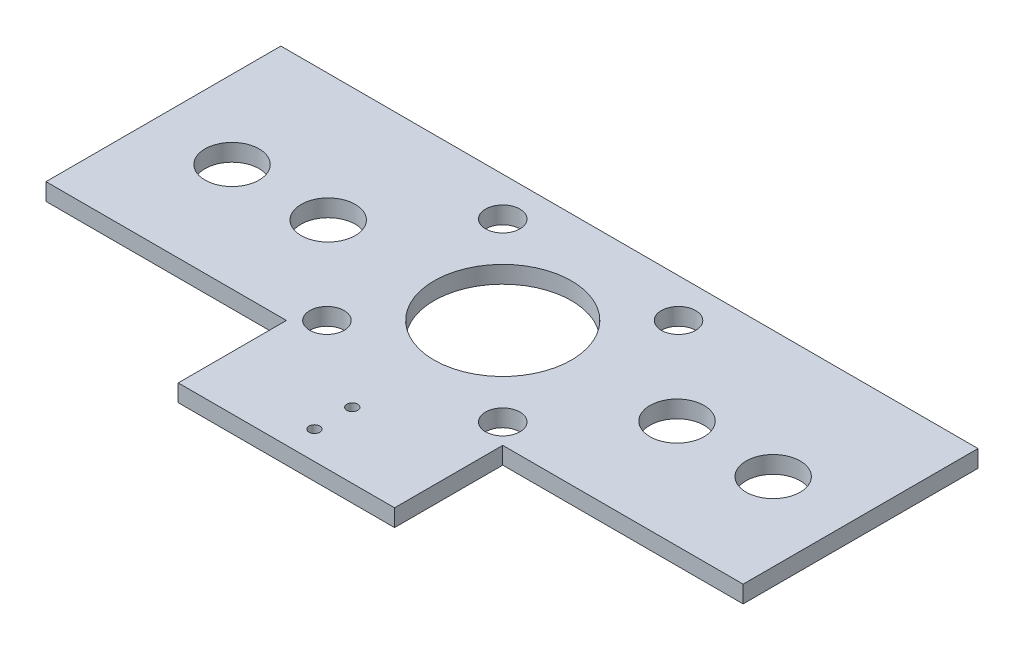
SolidWorks part; units mm, degrees
ref_plane "Front Plane" through (0, 0, 0) normal (0, 0, 1) x (1, 0, 0)
ref_plane "Top Plane" through (0, 0, 0) normal (0, 1, 0) x (1, 0, 0)
ref_plane "Right Plane" through (0, 0, 0) normal (1, 0, 0) x (0, 0, -1)
sketch "plateOutline" plane through (0, 0, 0) normal (0, 1, 0) x (1, 0, 0)
  line L0 (-40, 40) -> (-40, -40)
  line L1 (-40, -40) -> (40, -40)
  line L2 (-40, -40) -> (-40, 40)
  line L4 (40, -40) -> (40, 40)
  line L5 (-40, -40) -> (40, 40) construction
  line L6 (-40, 40) -> (40, -40) construction
  line L7 (-40, -40) -> (40, -40) construction
  line L8 (-40, -40) -> (-40, 40) construction
  line L9 (-40, 40) -> (40, 40) construction
  line L10 (40, -40) -> (40, 40) construction
  line L12 (-40, -40) -> (-128.9, -40)
  line L13 (-128.9, 40) -> (-128.9, -40)
  line L14 (40, 40) -> (40, -40)
  line L16 (40, -40) -> (128.9, -40)
  line L17 (128.9, 40) -> (128.9, -40)
  line L19 (-40, -40) -> (40, -40)
  line L20 (-40, -40) -> (-40, -80)
  line L21 (-40, -80) -> (40, -80)
  line L22 (40, -40) -> (40, -80)
  line L24 (-128.9, 40) -> (-128.9, 46.8499)
  line L25 (-128.9, 46.8499) -> (128.9, 46.8499)
  line L26 (128.9, 40) -> (128.9, 46.8499)
  point P0 (0, 0)
  dimension "D1" = 80
  dimension "D2" = 88.9
  dimension "D3" = 88.9
  dimension "D4" = 40
sketch "railGuides" plane through (0, 0, 0) normal (0, 1, 0) x (1, 0, 0)
  line L1 (-32.5, -32.5) -> (32.5, -32.5) construction
  line L2 (-32.5, -32.5) -> (-32.5, 32.5) construction
  line L3 (-32.5, 32.5) -> (32.5, 32.5) construction
  line L4 (32.5, -32.5) -> (32.5, 32.5) construction
  line L6 (-40, 40) -> (-25, 25) construction
  line L7 (40, 40) -> (25, 25) construction
  line L8 (25, -25) -> (40, -40) construction
  line L9 (-40, -40) -> (-25, -25) construction
  line L10 (-40, 40) -> (-25, 25) construction
  circle A0 centre (-32.5, 32.5) radius 6.35
  circle A1 centre (32.5, 32.5) radius 6.35
  circle A2 centre (32.5, -32.5) radius 6.35
  circle A3 centre (-32.5, -32.5) radius 6.35
sketch "FuelGrainMounting" plane through (0, 0, 0) normal (0, 1, 0) x (1, 0, 0)
  circle A0 centre (0, 0) radius 25.4
extrude "Boss-Extrude1" add sketch "plateOutline" along normal blind 6.35
extrude "Cut-Extrude1" cut sketch "railGuides" along normal blind 10
extrude "Cut-Extrude2" cut sketch "FuelGrainMounting" along normal blind 10
sketch "Sketch2" plane through (0, 0, 0) normal (0, 1, 0) x (1, 0, 0)
  line L0 (0, -69.63) -> (0, -55.63) construction
  line L1 (0, 0) -> (0, -69.63) construction
  circle A0 centre (0, -69.63) radius 2
  circle A1 centre (0, -55.63) radius 2
extrude "Cut-Extrude3" cut sketch "Sketch2" along normal blind 10
sketch "Sketch5" plane through (0, 0, 0) normal (0, 1, 0) x (1, 0, 0)
  circle A0 centre (-100, -0.0975) radius 10
  circle A1 centre (-64.45, -0.0975) radius 10
  circle A2 centre (64.45, 0) radius 10
  circle A3 centre (100, 0) radius 10
extrude "Cut-Extrude4" cut sketch "Sketch5" along normal blind 10
sketch "Sketch7" plane through (0, 6.35, 0) normal (0, 1, 0) x (1, 0, 0)
  line L0 (0, 0) -> (0, -69.63) construction
